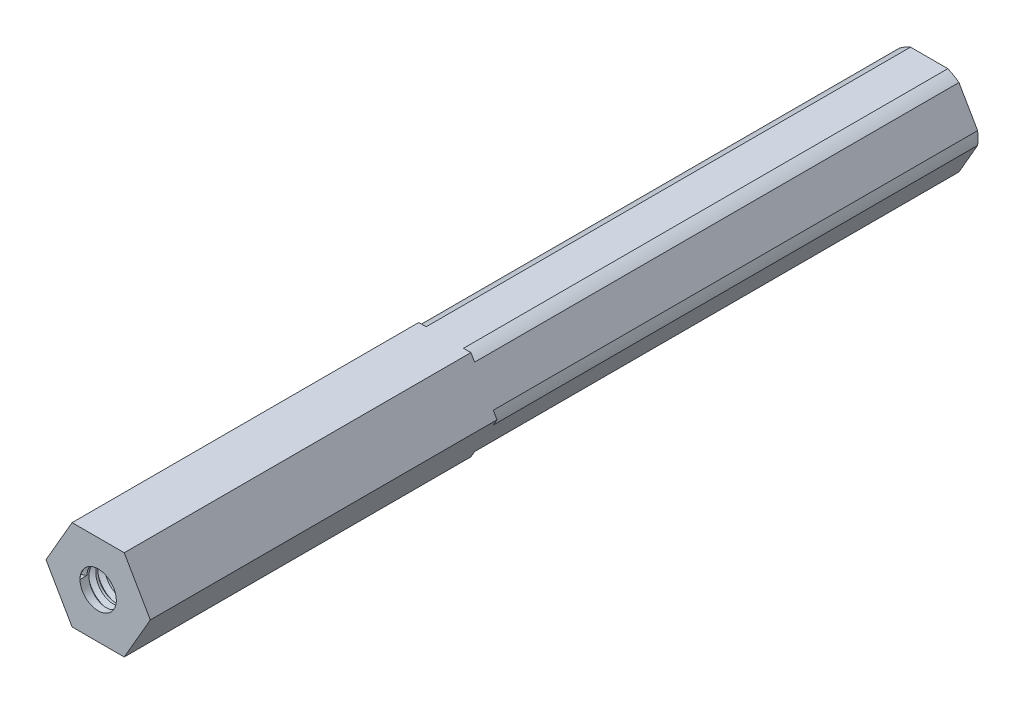
SolidWorks part; units mm, degrees
material "7075-T6 (SN)"
ref_plane "Alzado" through (0, 0, 0) normal (0, 0, 1) x (1, 0, 0)
ref_plane "Planta" through (0, 0, 0) normal (0, 1, 0) x (1, 0, 0)
ref_plane "Vista lateral" through (0, 0, 0) normal (1, 0, 0) x (0, 0, -1)
sketch "Croquis2" plane through (0, 0, 0) normal (0, 0, 1) x (1, 0, 0)
  line L1 (3.6662, -6.35) -> (7.3323, 0)
  line L2 (7.3323, 0) -> (3.6662, 6.35)
  line L3 (3.6662, 6.35) -> (-3.6662, 6.35)
  line L4 (-3.6662, 6.35) -> (-7.3323, 0)
  line L5 (-7.3323, 0) -> (-3.6662, -6.35)
  line L6 (-3.6662, -6.35) -> (3.6662, -6.35)
  circle A0 centre (0, 0) radius 6.35 construction
  dimension "D1" = 12.7
extrude "Extrusión Hex Profile" add sketch "Croquis2" along normal mid plane 116.84
sketch "Croquis3" plane through (0, 0, 0) normal (0, 0, 1) x (1, 0, 0)
  circle A0 centre (0, 0) radius 2.5527
  dimension "D1" = 5.1054
extrude "Tap Hole 1" cut sketch "Croquis3" against normal blind 19.05 from surface starting at face at (0, 0, 58.42)
extrude "Tap Hole 2" cut sketch "Croquis3<3>" along normal blind 19.05 from surface starting at face at (0, 0, -58.42)
sketch "Croquis3<3>" plane through (0, 0, 0) normal (0, 0, 1) x (1, 0, 0) same geometry as "Croquis3"
sketch "Croquis7" plane through (0, 0, 0) normal (0, 0, 1) x (1, 0, 0)
  circle A0 centre (0, 0) radius 6.8707
  dimension "D1" = 13.7414
extrude "ThunderHex" cut sketch "Croquis7" against normal through all and the other way offset from surface 48.7426 flip side to cut other way up to face at (2.5527, 0, 58.42)
sketch "Croquis8" plane through (0, 0, 0) normal (0, 1, 0) x (1, 0, 0)
  line L0 (0, -58.42) -> (-5.5562, -58.42) construction
  line L1 (3.6662, -58.42) -> (-3.6662, -58.42) construction
  line L3 (0, -58.42) -> (0, 0) construction
  line L4 (-5.5562, -58.42) -> (-6.35, -57.6263)
  line L5 (-6.35, -57.6263) -> (-6.35, -56.8325)
  line L6 (-6.35, -56.8325) -> (-5.9055, -56.8325)
  line L7 (-5.9055, -56.8325) -> (-5.9055, -55.245)
  line L8 (-5.9055, -55.245) -> (-12.7, -55.245)
  line L9 (-12.7, -55.245) -> (-12.7, -58.42)
  line L10 (-12.7, -58.42) -> (-5.5562, -58.42)
  line L11 (-3.6662, -58.42) -> (-7.3323, -58.42) construction
  dimension "D1" = 11.811
  dimension "D2" = 12.7
  dimension "D3" = 45
  dimension "D4" = 0.7937
  dimension "D6" = 0.7937
  dimension "D7" = 3.175
  dimension "D8" = 25.4
revolve "Retaining Ring 1" [suppressed] cut sketch "Croquis8" angle 360 about L3
sketch "Croquis9" plane through (0, 0, 0) normal (0, -1, 0) x (1, 0, 0)
  line L0 (0, -58.42) -> (-5.5562, -58.42) construction
  line L3 (0, -58.42) -> (0, 0) construction
  line L4 (-5.5562, -58.42) -> (-6.35, -57.6263)
  line L5 (-6.35, -57.6263) -> (-6.35, -56.8325)
  line L6 (-6.35, -56.8325) -> (-5.9055, -56.8325)
  line L7 (-5.9055, -56.8325) -> (-5.9055, -55.245)
  line L8 (-5.9055, -55.245) -> (-12.7, -55.245)
  line L9 (-12.7, -55.245) -> (-12.7, -58.42)
  line L10 (-12.7, -58.42) -> (-5.5562, -58.42)
  line L12 (-2.6237, -58.42) -> (2.6237, -58.42) construction
  line L13 (-6.8111, -58.42) -> (-4.1874, -58.42) construction
  dimension "D1" = 11.811
  dimension "D2" = 12.7
  dimension "D3" = 45
  dimension "D4" = 0.7937
  dimension "D6" = 0.7937
  dimension "D7" = 3.175
  dimension "D8" = 25.4
revolve "Retaining Ring 2" [suppressed] cut sketch "Croquis9" angle 360 about L3
sketch "Croquis10" plane through (0, 0, 0) normal (0, 1, 0) x (1, 0, 0)
  line L0 (0, -58.42) -> (0, 0) construction
  line L1 (3.6662, -58.42) -> (-3.6662, -58.42) construction
  line L2 (0, -58.42) -> (-5.5562, -58.42) construction
  line L3 (-3.6662, -58.42) -> (-7.3323, -58.42) construction
  line L4 (-5.5562, -58.42) -> (-6.35, -57.6263)
  line L5 (-6.35, -57.6263) -> (-6.35, -50.4698)
  line L6 (-6.35, -50.4698) -> (-9.525, -50.4698)
  line L7 (-9.525, -50.4698) -> (-9.525, -58.42)
  line L8 (-9.525, -58.42) -> (-5.5562, -58.42)
  dimension "D2" = 12.7
  dimension "D1" = 45
  dimension "D3" = 0.7937
  dimension "D4" = 7.9502
  dimension "D5" = 19.05
revolve "Round End 1" [suppressed] cut sketch "Croquis10" angle 360 about L0
sketch "Croquis12" plane through (0, 0, 0) normal (0, -1, 0) x (1, 0, 0)
  line L0 (0, -58.42) -> (0, 0) construction
  line L2 (0, -58.42) -> (-5.5562, -58.42) construction
  line L4 (-5.5562, -58.42) -> (-6.35, -57.6263)
  line L5 (-6.35, -57.6263) -> (-6.35, -50.4698)
  line L6 (-6.35, -50.4698) -> (-9.525, -50.4698)
  line L7 (-9.525, -50.4698) -> (-9.525, -58.42)
  line L8 (-9.525, -58.42) -> (-5.5562, -58.42)
  line L9 (-2.6237, -58.42) -> (2.6237, -58.42) construction
  dimension "D1" = 45
  dimension "D3" = 0.7937
  dimension "D4" = 7.9502
  dimension "D2" = 12.7
  dimension "D5" = 19.05
revolve "Round End 2" [suppressed] cut sketch "Croquis12" angle 360 about L0
thread "Rosca1" pitch 1.27 method cut profile "Perfil de rosca1" start angle 0, offset 0, length 0, pitch 1.27, diameter 5.1054
ref_plane "Plano1" through (-2.5527, 0, 58.42) normal (0, -1, 0) x (-1, 0, 0)
sketch "Perfil de rosca1" plane through (-2.5527, 0, 58.42) normal (0, -1, 0) x (-1, 0, 0)
  line L0 (0, 0) -> (0, 1.27) construction
  line L1 (0, 0) -> (0.6874, 0.3969)
  line L2 (0.6874, 0.3969) -> (0.6874, 0.5556)
  line L3 (0.6874, 0.5556) -> (0, 0.9525)
  line L4 (0.6874, 0.4762) -> (0, 0.4762) construction
  line L11 (0, 0) -> (0, 0.9525)
  point P2 (0, 0)
  dimension "Pitch" = 1.27
  dimension "Profile_Angle" = 60
  dimension "Profile_Land" = 0.1588
  dimension "Profile_Height" = 0.6874
thread "Rosca2" pitch 1.27 method cut profile "Perfil de rosca2" start angle 0, offset 0, length 0, pitch 1.27, diameter 5.1054
ref_plane "Plano2" through (2.5527, 0, -58.42) normal (0, -1, 0) x (1, 0, 0)
sketch "Perfil de rosca2" plane through (2.5527, 0, -58.42) normal (0, -1, 0) x (1, 0, 0)
  line L0 (0, 0) -> (0, 1.27) construction
  line L1 (0, 0) -> (0.6874, 0.3969)
  line L2 (0.6874, 0.3969) -> (0.6874, 0.5556)
  line L3 (0.6874, 0.5556) -> (0, 0.9525)
  line L4 (0.6874, 0.4762) -> (0, 0.4762) construction
  line L11 (0, 0) -> (0, 0.9525)
  point P2 (0, 0)
  dimension "Pitch" = 1.27
  dimension "Profile_Angle" = 60
  dimension "Profile_Land" = 0.1588
  dimension "Profile_Height" = 0.6874
equation "\"HexOD\"= 0.5pulgadas"
equation "\"Largo\" = 4.6pulgadas"
equation "\"D1@Croquis2\"=\"HexOD\""
equation "\"D1@Extrusión Hex Profile\" = \"Largo\""
equation "\"TapHole\"= IIF ( \"HexOD\" = 0.5pulgadas , 0.2010pulgadas , 0.190pulgadas )"
equation "\"D1@Croquis3\"=\"TapHole\""
equation "\"ProTapHole\"= 0.75pulgadas"
equation "\"D1@Tap Hole 1\" = \"ProTapHole\""
equation "\"D1@Tap Hole 2\" = \"ProTapHole\""
equation "\"ThunderHex\"= IIF ( \"HexOD\" = 0.5pulgadas , 0.541pulgadas , 0.4035pulgadas )"
equation "\"D1@Croquis7\"=\"ThunderHex\""
equation "\"D2@Croquis8\"=\"HexOD\""
equation "\"D1@Croquis8\"=if(\"HexOD\"=0.5pulgadas, 0.465pulgadas, 0.35pulgadas )"
equation "\"D2@Croquis9\"=\"HexOD\""
equation "\"D1@Croquis9\"=if(\"HexOD\"=0.5pulgadas, 0.465pulgadas, 0.35pulgadas )"
equation "\"D8@Croquis8\"=\"HexOD\"*2"
equation "\"D8@Croquis9\"=\"HexOD\"*2"
equation "\"D5@Croquis10\"=\"HexOD\"*1.5"
equation "\"D5@Croquis12\"=\"HexOD\"*1.5"
equation "\"D4@Croquis10\"=if( \"D2@Croquis10\"=<0.375, 0.28, 0.313)"
equation "\"D4@Croquis12\"=if( \"D2@Croquis10\"=<0.375, 0.28, 0.313)"
